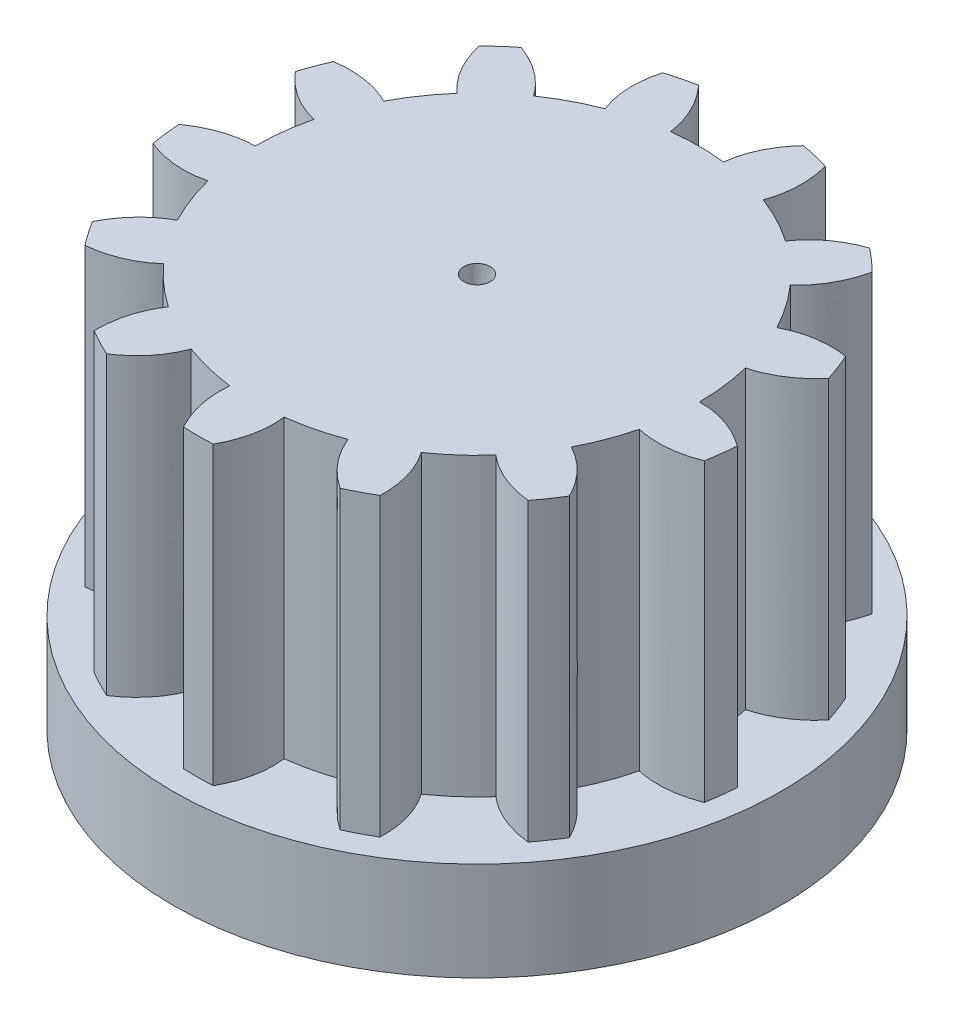
SolidWorks part; units mm, degrees
ref_plane "Front Plane" through (0, 0, 0) normal (0, 0, 1) x (1, 0, 0)
ref_plane "Top Plane" through (0, 0, 0) normal (0, 1, 0) x (1, 0, 0)
ref_plane "Right Plane" through (0, 0, 0) normal (1, 0, 0) x (0, 0, -1)
sketch "Sketch1" plane through (0, 0, 0) normal (0, 1, 0) x (1, 0, 0)
  line L0 (0, 0) -> (0, 17.0926) construction
  line L1 (0, 0) -> (3.5061, 14.2208) construction
  line L2 (0, 0) -> (1.9234, 15.8361) construction
  line L3 (0, 0) -> (4.6786, 12.3295) construction
  circle A3 centre (0, 0) radius 0.4
  arc A4 (-5.0652, 4.4616) -> (-5.9762, 3.138) centre (0, 0) ccw
  arc A6 (-2.4116, 6.3045) -> (-3.8334, 5.5559) centre (0, 0) ccw
  arc A7 (0.8138, 6.7008) -> (-0.8124, 6.7009) centre (0, 0) ccw
  arc A8 (3.8185, 5.5661) -> (2.3948, 6.3109) centre (0, 0) ccw
  arc A9 (5.9678, 3.154) -> (5.0533, 4.4751) centre (0, 0) ccw
  arc A10 (6.75, 0.0193) -> (6.5542, 1.6141) centre (0, 0) ccw
  arc A11 (5.9858, -3.1198) -> (6.5536, -1.6166) centre (0, 0) ccw
  arc A12 (3.8503, -5.5442) -> (5.0516, -4.477) centre (0, 0) ccw
  arc A13 (0.8328, -6.6984) -> (2.3924, -6.3118) centre (0, 0) ccw
  arc A14 (-2.3755, -6.3182) -> (-0.8149, -6.7006) centre (0, 0) ccw
  arc A15 (-5.0396, -4.4905) -> (-3.8355, -5.5544) centre (0, 0) ccw
  arc A16 (-6.5492, -1.6341) -> (-5.9774, -3.1358) centre (0, 0) ccw
  arc A17 (-6.5585, 1.5966) -> (-6.75, 0.0013) centre (0, 0) ccw
  arc A18 (-7.781, 3.4215) -> (-8.1003, 2.5759) centre (0, 0) ccw
  arc A19 (-8.4797, -0.5864) -> (-8.3695, -1.4836) centre (0, 0) ccw
  arc A20 (-7.2359, -4.46) -> (-6.7214, -5.2032) centre (0, 0) ccw
  arc A21 (-4.3344, -7.3118) -> (-3.5335, -7.7308) centre (0, 0) ccw
  arc A22 (-5.2996, 6.6456) -> (-5.9754, 6.0452) centre (0, 0) ccw
  arc A23 (-1.6043, 8.3472) -> (-2.4816, 8.1297) centre (0, 0) ccw
  arc A24 (8.3737, -1.46) -> (8.4814, -0.5625) centre (0, 0) ccw
  arc A25 (8.093, 2.5987) -> (7.7713, 3.4434) centre (0, 0) ccw
  arc A28 (2.4587, 8.1366) -> (1.5807, 8.3517) centre (0, 0) ccw
  arc A31 (5.9583, 6.062) -> (5.2809, 6.6605) centre (0, 0) ccw
  arc A32 (6.736, -5.1842) -> (7.2485, -4.4396) centre (0, 0) ccw
  arc A33 (3.5553, -7.7208) -> (4.355, -7.2996) centre (0, 0) ccw
  arc A34 (-0.44, -8.4886) -> (0.4639, -8.4873) centre (0, 0) ccw
  spline S0 degree 3 poles (0.633, 5.2117) (0.7252, 5.9828) (1.0144, 6.8191) (1.6201, 7.3229) knots 0 0 0 0 1 1 1 1 construction
  spline S1 degree 1 poles (1.6201, 7.3229) (1.9696, 7.2368) knots 0 0 1 1 construction
  spline S2 degree 3 poles (1.8622, 4.9086) (2.139, 5.6342) (2.2717, 6.5091) (1.9696, 7.2368) knots 0 0 0 0 1 1 1 1 construction
  spline S3 degree 3 poles (3.93, 3.481) (4.5123, 3.9948) (5.0364, 4.7079) (5.1071, 5.4925) knots 0 0 0 0 1 1 1 1 construction
  spline S4 degree 3 poles (2.9825, 4.3206) (3.4225, 4.9605) (4.0672, 5.5666) (4.8376, 5.7313) knots 0 0 0 0 1 1 1 1 construction
  spline S5 degree 1 poles (4.8376, 5.7313) (5.1071, 5.4925) knots 0 0 1 1 construction
  spline S6 degree 3 poles (5.0976, 1.2559) (5.852, 1.4403) (6.6474, 1.8281) (7.0746, 2.49) knots 0 0 0 0 1 1 1 1 construction
  spline S7 degree 3 poles (4.6487, 2.4397) (5.3357, 2.8018) (6.1883, 3.0389) (6.947, 2.8266) knots 0 0 0 0 1 1 1 1 construction
  spline S8 degree 1 poles (6.947, 2.8266) (7.0746, 2.49) knots 0 0 1 1 construction
  spline S9 degree 3 poles (5.0973, -1.2569) (5.851, -1.4442) (6.7355, -1.4705) (7.4214, -1.083) knots 0 0 0 0 1 1 1 1 construction
  spline S10 degree 3 poles (5.25, -0.0002) (6.0266, 0.0012) (6.8917, -0.1851) (7.4648, -0.7256) knots 0 0 0 0 1 1 1 1 construction
  spline S11 degree 1 poles (7.4648, -0.7256) (7.4214, -1.083) knots 0 0 1 1 construction
  spline S12 degree 3 poles (3.9293, -3.4818) (4.5096, -3.9979) (5.2806, -4.4322) (6.068, -4.4078) knots 0 0 0 0 1 1 1 1 construction
  spline S13 degree 3 poles (4.6486, -2.4399) (5.3369, -2.7996) (6.0163, -3.3666) (6.2726, -4.1115) knots 0 0 0 0 1 1 1 1 construction
  spline S14 degree 1 poles (6.2726, -4.1115) (6.068, -4.4078) knots 0 0 1 1 construction
  spline S15 degree 3 poles (1.8612, -4.909) (2.1351, -5.6357) (2.616, -6.3786) (3.3246, -6.7229) knots 0 0 0 0 1 1 1 1 construction
  spline S16 degree 3 poles (2.9822, -4.3208) (3.4245, -4.9591) (3.7626, -5.7769) (3.6434, -6.5556) knots 0 0 0 0 1 1 1 1 construction
  spline S17 degree 1 poles (3.6434, -6.5556) (3.3246, -6.7229) knots 0 0 1 1 construction
  spline S18 degree 3 poles (-0.6334, -5.2117) (-0.7285, -5.9824) (-0.6479, -6.8636) (-0.1805, -7.4978) knots 0 0 0 0 1 1 1 1 construction
  spline S19 degree 3 poles (0.6327, -5.2117) (0.7277, -5.9825) (0.647, -6.8637) (0.1795, -7.4979) knots 0 0 0 0 1 1 1 1 construction
  spline S20 degree 1 poles (0.1795, -7.4979) (-0.1805, -7.4978) knots 0 0 1 1 construction
  spline S21 degree 3 poles (-2.9828, -4.3204) (-3.4252, -4.9586) (-3.7634, -5.7764) (-3.6443, -6.5551) knots 0 0 0 0 1 1 1 1 construction
  spline S22 degree 3 poles (-1.8618, -4.9088) (-2.1359, -5.6354) (-2.6168, -6.3782) (-3.3255, -6.7224) knots 0 0 0 0 1 1 1 1 construction
  spline S23 degree 1 poles (-3.3255, -6.7224) (-3.6443, -6.5551) knots 0 0 1 1 construction
  spline S24 degree 3 poles (-4.6489, -2.4393) (-5.3372, -2.7989) (-6.0167, -3.3658) (-6.2731, -4.1107) knots 0 0 0 0 1 1 1 1 construction
  spline S25 degree 3 poles (-3.9298, -3.4813) (-4.5101, -3.9973) (-5.2812, -4.4315) (-6.0686, -4.407) knots 0 0 0 0 1 1 1 1 construction
  spline S26 degree 1 poles (-6.0686, -4.407) (-6.2731, -4.1107) knots 0 0 1 1 construction
  spline S27 degree 3 poles (-5.25, 0.0006) (-6.0266, 0.0021) (-6.8917, -0.1841) (-7.4649, -0.7246) knots 0 0 0 0 1 1 1 1 construction
  spline S28 degree 3 poles (-5.0975, -1.2563) (-5.8512, -1.4435) (-6.7357, -1.4696) (-7.4215, -1.082) knots 0 0 0 0 1 1 1 1 construction
  spline S29 degree 1 poles (-7.4215, -1.082) (-7.4649, -0.7246) knots 0 0 1 1 construction
  spline S30 degree 3 poles (-4.6484, 2.4403) (-5.3353, 2.8025) (-6.1879, 3.0397) (-6.9466, 2.8276) knots 0 0 0 0 1 1 1 1 construction
  spline S31 degree 3 poles (-5.0974, 1.2566) (-5.8518, 1.441) (-6.6471, 1.829) (-7.0743, 2.4909) knots 0 0 0 0 1 1 1 1 construction
  spline S32 degree 1 poles (-7.0743, 2.4909) (-6.9466, 2.8276) knots 0 0 1 1 construction
  spline S33 degree 3 poles (-2.9819, 4.321) (-3.4218, 4.9609) (-4.0665, 5.5672) (-4.8369, 5.7319) knots 0 0 0 0 1 1 1 1 construction
  spline S34 degree 3 poles (-3.9296, 3.4815) (-4.5118, 3.9954) (-5.0358, 4.7085) (-5.1064, 5.4932) knots 0 0 0 0 1 1 1 1 construction
  spline S35 degree 1 poles (-5.1064, 5.4932) (-4.8369, 5.7319) knots 0 0 1 1 construction
  spline S36 degree 3 poles (-0.6323, 5.2118) (-0.7244, 5.9829) (-1.0135, 6.8193) (-1.6191, 7.3232) knots 0 0 0 0 1 1 1 1 construction
  spline S37 degree 3 poles (-1.8615, 4.9089) (-2.1382, 5.6345) (-2.2708, 6.5094) (-1.9686, 7.237) knots 0 0 0 0 1 1 1 1 construction
  spline S38 degree 1 poles (-1.9686, 7.237) (-1.6191, 7.3232) knots 0 0 1 1 construction
  spline S39 degree 3 poles (-4.6484, 2.4403) (-4.4519, 2.8146) (-4.2099, 3.1651) (-3.9296, 3.4815) knots 0 0 0 0 0.038449 0.038449 0.038449 0.038449 construction
  spline S40 degree 3 poles (-2.9819, 4.321) (-2.6339, 4.5611) (-2.2568, 4.759) (-1.8615, 4.9089) knots 0.076923 0.076923 0.076923 0.076923 0.115372 0.115372 0.115372 0.115372 construction
  spline S41 degree 3 poles (-0.6323, 5.2118) (-0.2126, 5.2627) (0.2133, 5.2627) (0.633, 5.2117) (0.633, 5.2117) knots 0.153846 0.153846 0.153846 0.153846 0.192296 0.192296 0.192296 0.192296 0.192296 construction
  spline S42 degree 3 poles (-5.25, 0.0006) (-5.25, 0.4233) (-5.1986, 0.8461) (-5.0974, 1.2566) knots 0.923077 0.923077 0.923077 0.923077 0.961526 0.961526 0.961526 0.961526 construction
  spline S43 degree 3 poles (-4.6489, -2.4393) (-4.8453, -2.0649) (-4.9963, -1.6667) (-5.0975, -1.2563) knots 0.846154 0.846154 0.846154 0.846154 0.884603 0.884603 0.884603 0.884603 construction
  spline S44 degree 3 poles (-2.9828, -4.3204) (-3.3307, -4.0802) (-3.6494, -3.7977) (-3.9298, -3.4813) knots 0.769231 0.769231 0.769231 0.769231 0.80768 0.80768 0.80768 0.80768 construction
  spline S45 degree 3 poles (-0.6334, -5.2117) (-1.053, -5.1607) (-1.4665, -5.0587) (-1.8618, -4.9088) knots 0.692308 0.692308 0.692308 0.692308 0.730757 0.730757 0.730757 0.730757 construction
  spline S46 degree 3 poles (1.8612, -4.909) (1.4659, -5.0589) (1.0524, -5.1608) (0.6327, -5.2117) knots 0.615385 0.615385 0.615385 0.615385 0.653834 0.653834 0.653834 0.653834 construction
  spline S47 degree 3 poles (3.9293, -3.4818) (3.6489, -3.7982) (3.3302, -4.0806) (2.9822, -4.3208) knots 0.538462 0.538462 0.538462 0.538462 0.576911 0.576911 0.576911 0.576911 construction
  spline S48 degree 3 poles (5.0973, -1.2569) (4.9961, -1.6674) (4.8451, -2.0656) (4.6486, -2.4399) knots 0.461538 0.461538 0.461538 0.461538 0.499988 0.499988 0.499988 0.499988 construction
  spline S49 degree 3 poles (5.0976, 1.2559) (5.1987, 0.8454) (5.25, 0.4226) (5.25, -0.0002) knots 0.384615 0.384615 0.384615 0.384615 0.423065 0.423065 0.423065 0.423065 construction
  spline S50 degree 3 poles (3.93, 3.481) (4.2104, 3.1645) (4.4523, 2.814) (4.6487, 2.4397) knots 0.307692 0.307692 0.307692 0.307692 0.346142 0.346142 0.346142 0.346142 construction
  spline S51 degree 3 poles (1.8622, 4.9086) (2.2575, 4.7587) (2.6345, 4.5607) (2.9825, 4.3206) knots 0.230769 0.230769 0.230769 0.230769 0.269219 0.269219 0.269219 0.269219 construction
  spline S52 degree 3 poles (0.7945, 6.7031) (0.8653, 7.3126) (1.1274, 7.8622) (1.5807, 8.3517) knots 0 0 0 0 0.872429 0.872429 0.872429 0.872429
  spline S53 degree 3 poles (2.4587, 8.1366) (2.623, 7.4967) (2.6017, 6.8881) (2.3948, 6.3109) knots 0.127683 0.127683 0.127683 0.127683 1 1 1 1
  spline S54 degree 3 poles (3.8185, 5.5661) (4.1646, 6.0729) (4.652, 6.4377) (5.2809, 6.6605) knots 0 0 0 0 0.872429 0.872429 0.872429 0.872429
  spline S55 degree 3 poles (5.9583, 6.062) (5.8065, 5.419) (5.5048, 4.89) (5.0533, 4.4751) knots 0.127683 0.127683 0.127683 0.127683 1 1 1 1
  spline S56 degree 3 poles (5.9678, 3.154) (6.5097, 3.4419) (7.1109, 3.5384) (7.7713, 3.4434) knots 0 0 0 0 0.872429 0.872429 0.872429 0.872429
  spline S57 degree 3 poles (8.093, 2.5987) (7.6597, 2.0999) (7.1468, 1.7717) (6.5542, 1.6141) knots 0.127683 0.127683 0.127683 0.127683 1 1 1 1
  spline S58 degree 3 poles (6.75, 0.0193) (7.3636, 0.0224) (7.9407, -0.1715) (8.4814, -0.5625) knots 0 0 0 0 0.872429 0.872429 0.872429 0.872429
  spline S59 degree 3 poles (8.3737, -1.46) (7.7582, -1.7003) (7.1515, -1.7525) (6.5536, -1.6166) knots 0.127683 0.127683 0.127683 0.127683 1 1 1 1
  spline S60 degree 3 poles (5.9858, -3.1198) (6.5306, -3.4022) (6.9515, -3.8421) (7.2485, -4.4396) knots 0 0 0 0 0.872429 0.872429 0.872429 0.872429
  spline S61 degree 3 poles (6.736, -5.1842) (6.0794, -5.1109) (5.5179, -4.8752) (5.0516, -4.477) knots 0.127683 0.127683 0.127683 0.127683 1 1 1 1
  spline S62 degree 3 poles (3.8503, -5.5442) (4.2015, -6.0474) (4.3697, -6.6325) (4.355, -7.2996) knots 0 0 0 0 0.872429 0.872429 0.872429 0.872429
  spline S63 degree 3 poles (3.5553, -7.7208) (3.0079, -7.3508) (2.6202, -6.8811) (2.3924, -6.3118) knots 0.127683 0.127683 0.127683 0.127683 1 1 1 1
  spline S64 degree 3 poles (0.8328, -6.6984) (0.9098, -7.3072) (0.7869, -7.9035) (0.4639, -8.4873) knots 0 0 0 0 0.872429 0.872429 0.872429 0.872429
  spline S65 degree 3 poles (-0.44, -8.4886) (-0.7527, -7.9066) (-0.8777, -7.3106) (-0.8149, -6.7006) knots 0.127683 0.127683 0.127683 0.127683 1 1 1 1
  spline S66 degree 3 poles (-2.3755, -6.3182) (-2.5902, -6.8931) (-2.9762, -7.3639) (-3.5335, -7.7308) knots 0 0 0 0 0.872429 0.872429 0.872429 0.872429
  spline S67 degree 3 poles (-4.3344, -7.3118) (-4.3409, -6.6511) (-4.1746, -6.0653) (-3.8355, -5.5544) knots 0.127683 0.127683 0.127683 0.127683 1 1 1 1
  spline S68 degree 3 poles (-5.0396, -4.4905) (-5.4969, -4.8998) (-6.0575, -5.1373) (-6.7214, -5.2032) knots 0 0 0 0 0.872429 0.872429 0.872429 0.872429
  spline S69 degree 3 poles (-7.2359, -4.46) (-6.9346, -3.872) (-6.5151, -3.4306) (-5.9774, -3.1358) knots 0.127683 0.127683 0.127683 0.127683 1 1 1 1
  spline S70 degree 3 poles (-6.5492, -1.6341) (-7.1443, -1.784) (-7.751, -1.7338) (-8.3695, -1.4836) knots 0 0 0 0 0.872429 0.872429 0.872429 0.872429
  spline S71 degree 3 poles (-8.4797, -0.5864) (-7.9397, -0.2058) (-7.3631, -0.0099) (-6.75, 0.0013) knots 0.127683 0.127683 0.127683 0.127683 1 1 1 1
  spline S72 degree 3 poles (-6.5585, 1.5966) (-7.155, 1.7405) (-7.669, 2.0669) (-8.1003, 2.5759) knots 0 0 0 0 0.872429 0.872429 0.872429 0.872429
  spline S73 degree 3 poles (-7.781, 3.4215) (-7.1259, 3.5075) (-6.5243, 3.413) (-5.9762, 3.138) knots 0.127683 0.127683 0.127683 0.127683 1 1 1 1
  spline S74 degree 3 poles (-5.0652, 4.4616) (-5.5266, 4.8662) (-5.83, 5.3941) (-5.9754, 6.0452) knots 0 0 0 0 0.872429 0.872429 0.872429 0.872429
  spline S75 degree 3 poles (-5.2996, 6.6456) (-4.6796, 6.4173) (-4.1909, 6.0541) (-3.8334, 5.5559) knots 0.127683 0.127683 0.127683 0.127683 1 1 1 1
  spline S76 degree 3 poles (-2.4116, 6.3045) (-2.6321, 6.8771) (-2.6555, 7.4855) (-2.4816, 8.1297) knots 0 0 0 0 0.872429 0.872429 0.872429 0.872429
  spline S77 degree 3 poles (-1.6043, 8.3472) (-1.1613, 7.857) (-0.8973, 7.3082) (-0.8124, 6.7009) knots 0.127683 0.127683 0.127683 0.127683 1 1 1 1
  point P62 (1.792, 8.5633)
  point P64 (0, 0)
  point P66 (2.3745, 8.4197)
  point P121 (0, 0)
  dimension "D2" = 13.5
  dimension "D3" = 0.31
  dimension "D4" = 0.8
  dimension "D9" = 17
  dimension "D5" = 13.85
  dimension "D6" = 6.925
  dimension "D7" = 6.93
  dimension "D8" = 0.6
extrude "Boss-Extrude1" add sketch "Sketch1" along normal blind 9 contours S77 S76 A6 S75 S74 A4 S73 S72 A17 S71 S70 A16 S69 S68 A15 S67 S66 A14 S65 S64 A13 S63 S62 A12 S61 S60 A11 S59 S58 A10 S57 S56 A9 S55 S54 A8 S53 S52 region at (-5.4408, 0, -5.2965)
sketch "Sketch2" plane through (0, 0, 0) normal (0, -1, 0) x (1, 0, 0)
  circle A1 centre (0, 0) radius 9.25
  dimension "D1" = 18.5
extrude "Boss-Extrude2" add sketch "Sketch2" along normal blind 3
scale "Scale1" scale about centroid uniform scaling yes scale factor 1.8
sketch "Sketch3" plane through (0, -7.3822, 0) normal (0, -1, 0) x (1, 0, 0)
  line L0 (-10.1481, 10.074) -> (-0.1837, 3.4451)
  line L2 (3.3558, 0.8009) -> (12.5385, -6.8743)
  line L4 (10.1481, -10.074) -> (0.1837, -3.4451)
  line L6 (-3.3558, -0.8009) -> (-12.5385, 6.8743)
  arc A0 (-12.5385, 6.8743) -> (-10.1481, 10.074) centre (-11.2558, 8.4088) cw
  arc A1 (-0.1837, 3.4451) -> (3.3558, 0.8009) centre (0, 0) cw
  arc A2 (-3.3558, -0.8009) -> (0.1837, -3.4451) centre (0, 0) ccw
  arc A3 (10.1481, -10.074) -> (12.5385, -6.8743) centre (11.2558, -8.4088) ccw
extrude "Cut-Extrude1" cut sketch "Sketch3" against normal blind 2
